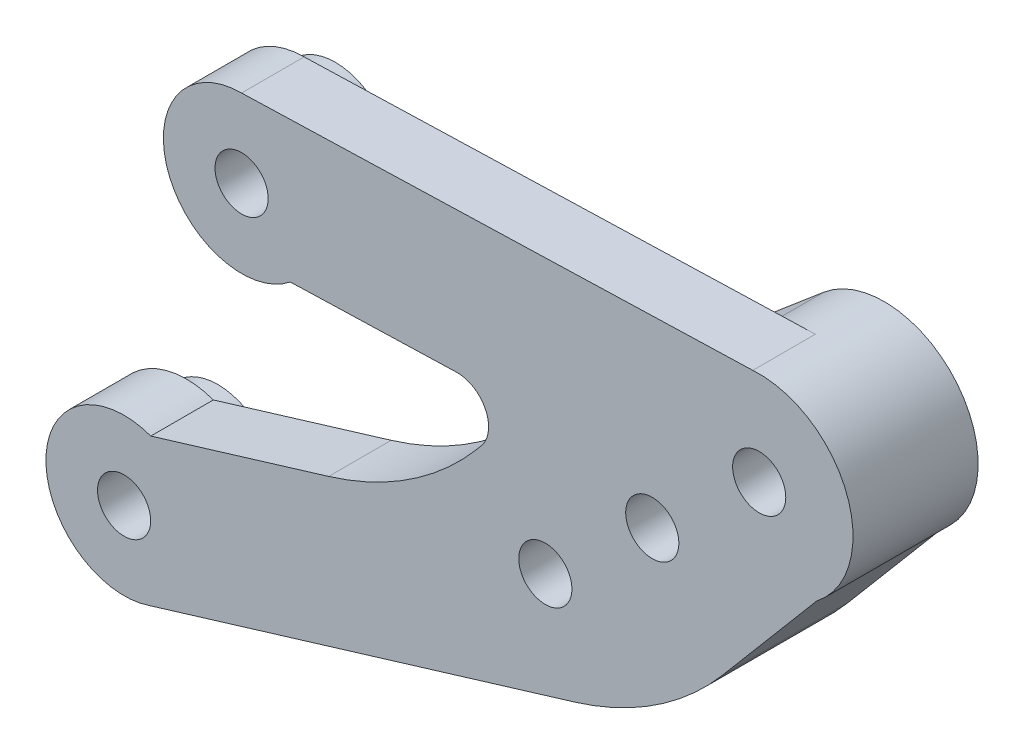
SolidWorks part; units mm, degrees
ref_plane "Front Plane" through (0, 0, 0) normal (0, 0, 1) x (1, 0, 0)
ref_plane "Top Plane" through (0, 0, 0) normal (0, 1, 0) x (1, 0, 0)
ref_plane "Right Plane" through (0, 0, 0) normal (1, 0, 0) x (0, 0, -1)
sketch "Sketch2" plane through (0, 0, 0) normal (0, 0, 1) x (1, 0, 0)
  line L0 (0, 0) -> (0, 21.6008) construction
  line L1 (40.6129, 21.6008) -> (0, 21.6008) construction
  line L2 (0, 0) -> (0, 21.6008) construction
  line L3 (0, 21.6008) -> (7.5129, 21.6008) construction
  line L4 (1.5758, -4.7452) -> (34.4569, 5.2326)
  line L5 (34.4569, 5.2326) -> (44.2966, 16.8647)
  line L6 (7.5129, 26.6008) -> (40.2038, 27.5868)
  line L10 (25.7338, 18.1463) -> (18.7287, 9.8651)
  line L11 (18.7287, 9.8651) -> (1.7066, 4.6997)
  line L12 (10.6292, 17.6907) -> (25.7338, 18.1463)
  circle A0 centre (0, 0) radius 1.7
  circle A1 centre (40.6129, 21.6008) radius 1.7
  circle A2 centre (7.5129, 21.6008) radius 1.7
  arc A3 (1.7066, 4.6997) -> (1.5758, -4.7452) centre (0, 0) ccw
  arc A4 (44.2966, 16.8647) -> (40.2038, 27.5868) centre (40.6129, 21.6008) ccw
  arc A5 (7.5129, 26.6008) -> (10.6292, 17.6907) centre (7.5129, 21.6008) ccw
  dimension "D1" = 3.4
  dimension "D2" = 3.4
  dimension "D3" = 3.4
  dimension "D8" = 10
  dimension "D9" = 12
  dimension "D10" = 10
  dimension "D4" = 46
  dimension "D5" = 33.1
  dimension "D7" = 22.87
  dimension "D11" = 9
  dimension "D12" = 9
  dimension "D13" = 15
extrude "Boss-Extrude1" add sketch "Sketch2" along normal blind 2 and the other way blind 2 contours L6 A5 A3 L4 L5 A4 A0 A1 A2 region at (22.1673, 13.7132, 0)
fillet "Fillet1" radius 20 2 edges at (34.4569, 5.2326, 0) (18.7287, 9.8651, 0)
sketch "Sketch3" plane through (0, 0, 2) normal (0, 0, 1) x (1, 0, 0)
  line L0 (44.2966, 16.8647) -> (30.687, 0.776)
  line L1 (38.2697, 9.7399) -> (44.2966, 16.8647) construction
  line L2 (30.687, 0.776) -> (37.0794, -4.6314)
  line L3 (37.0794, -4.6314) -> (43.0769, 2.4586)
  line L4 (44.2966, 16.8647) -> (50.689, 11.4573)
  line L5 (50.689, 11.4573) -> (44.6915, 4.3673)
  line L6 (43.0769, 2.4586) -> (32.5644, 0.4977)
  line L7 (32.5644, 0.4977) -> (44.8824, 15.0595)
  line L8 (44.8824, 15.0595) -> (44.6915, 4.3673)
  line L9 (32.5644, 0.4977) -> (31.9186, -0.2658) construction
  line L10 (44.8824, 15.0595) -> (45.5282, 15.8229) construction
  dimension "D1" = 1
  dimension "D2" = 2.5
extrude "Boss-Extrude2" [suppressed] add sketch "Sketch3" against normal up to surface (10 mm away)
fillet "Fillet2" [suppressed] radius 1
sketch "Sketch4" plane through (0, 0, 2) normal (0, 0, 1) x (1, 0, 0)
  line L7 (38.2697, 9.7399) -> (44.2966, 16.8647) construction
  line L8 (0, 0) -> (50000, 0) construction
  line L17 (44.2966, 16.8647) -> (44.8756, 15.9348)
  line L18 (40.6475, 27.6007) -> (47.8271, 27.6007)
  line L19 (47.8271, 27.6007) -> (51.8229, 19.889)
  line L20 (51.0994, 17.0478) -> (51.7638, 16.0989)
  line L21 (48.2447, 15.0489) -> (48.9091, 14.1)
  line L22 (48.3535, 17.9314) -> (-28630.4683, 40975.5336) construction
  arc A0 (40.6475, 27.6007) -> (44.2966, 16.8647) centre (40.6129, 21.6008) cw
  arc A1 (44.2966, 16.8647) -> (40.2038, 27.5868) centre (40.6129, 21.6008) ccw construction
  arc A3 (48.2447, 15.0489) -> (51.0994, 17.0478) centre (48.2713, 18.0488) ccw
  arc A4 (44.8756, 15.9348) -> (51.7638, 16.0989) centre (48.2713, 18.0488) ccw
  arc A5 (48.9091, 14.1) -> (51.8229, 19.889) centre (48.2713, 18.0488) ccw
  dimension "D1" = 6
  dimension "D2" = 8
  dimension "D3" = 55
extrude "Boss-Extrude3" [suppressed] add sketch "Sketch4" against normal up to surface (4 mm away)
fillet "Fillet3" [suppressed] radius 6
sketch "Sketch7" plane through (0, 0, -2) normal (0, 0, -1) x (-1, 0, 0)
  line L0 (-38.2697, 9.7399) -> (-44.2966, 16.8647) construction
  line L1 (-1.5758, -4.7452) -> (-28.8077, 3.5184) construction
  line L2 (-36.7334, 26.1779) -> (-21.684, 13.4222)
  line L4 (-44.2966, 16.8647) -> (-38.2697, 9.7399)
  line L6 (-40.6129, 21.6008) -> (-26.9361, 9.686) construction
  arc A2 (-38.2697, 9.7399) -> (-28.8077, 3.5184) centre (-23.0001, 22.6566) ccw
  arc A3 (-36.7334, 26.1779) -> (-44.2966, 16.8647) centre (-40.6129, 21.6008) ccw
  arc A4 (-28.8077, 3.5184) -> (-21.684, 13.4222) centre (-26.9361, 9.686) ccw
  arc A5 (-22.5414, 14.3724) -> (-13.0794, 8.1508) centre (-7.2719, 27.2891) ccw construction
  circle A6 centre (-40.6129, 21.6008) radius 1.7
  arc A7 (-40.2038, 27.5868) -> (-44.2966, 16.8647) centre (-40.6129, 21.6008) ccw construction
  point P5 (-33.0604, 15.194)
  point P10 (0, 0)
  point P21 (-28.8077, 3.5184)
extrude "Boss-Extrude4" add sketch "Sketch7" along normal blind 4
sketch "Sketch8" plane through (0, 0, -2) normal (0, 0, -1) x (-1, 0, 0)
  circle A0 centre (-7.5129, 21.6008) radius 1.7
  circle A1 centre (-7.5129, 21.6008) radius 3.7
  circle A2 centre (0, 0) radius 1.7
  circle A3 centre (0, 0) radius 3.7
  dimension "D1" = 2
  dimension "D2" = 2
  dimension "D3" = 3.4
  dimension "D4" = 3.4
extrude "Boss-Extrude5" add sketch "Sketch8" along normal blind 2
fillet "Fillet4" radius 2 1 edges at (25.7338, 18.1463, 0)
sketch "Sketch9" plane through (0, 0, -6) normal (0, 0, -1) x (-1, 0, 0)
  line L0 (-40.6129, 21.6008) -> (-26.9361, 9.686) construction
  circle A0 centre (-33.774, 15.643) radius 1.7
  arc A2 (-28.8077, 3.5184) -> (-21.684, 13.4222) centre (-26.9361, 9.686) ccw construction
  circle A3 centre (-26.9361, 9.686) radius 1.7
  dimension "D1" = 3.4
  dimension "D2" = 3.4
  dimension "D3" = 9.07
extrude "Cut-Extrude1" cut sketch "Sketch9" against normal through all
